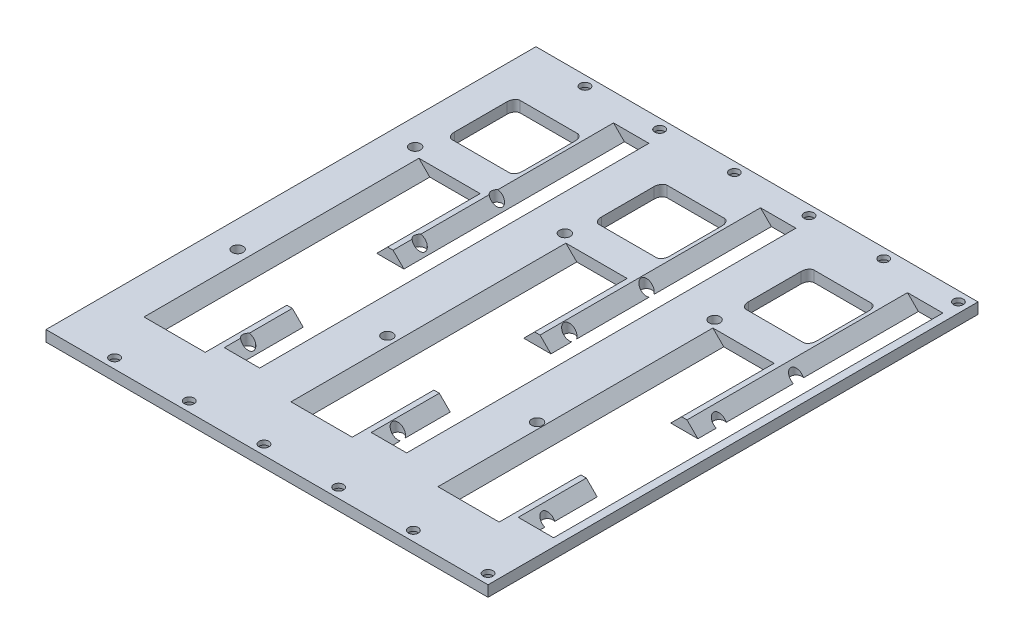
SolidWorks part; units mm, degrees
ref_plane "Płaszczyzna przednia" through (0, 0, 0) normal (0, 0, 1) x (1, 0, 0)
ref_plane "Płaszczyzna górna" through (0, 0, 0) normal (0, 1, 0) x (1, 0, 0)
ref_plane "Płaszczyzna prawa" through (0, 0, 0) normal (1, 0, 0) x (0, 0, -1)
sketch "Szkic1" plane through (0, 0, 0) normal (0, 1, 0) x (1, 0, 0)
  line L1 (-81.2, -90) -> (81.2, -90)
  line L2 (-81.2, -90) -> (-81.2, 90)
  line L3 (-81.2, 90) -> (81.2, 90)
  line L4 (81.2, -90) -> (81.2, 90)
  line L5 (0, 90) -> (0, -90) construction
  line L6 (-81.2, 0) -> (81.2, 0) construction
  point P0 (0, 0)
  dimension "D1" = 162.4
  dimension "D2" = 180
extrude "Dodanie-wyciągnięcie1" add sketch "Szkic1" along normal blind 4
sketch "Szkic2" plane through (0, 0, 0) normal (0, -1, 0) x (1, 0, 0)
  line L0 (-44, -47.8284) -> (-44, -67.1716) construction
  line L1 (-46, -70) -> (-67, -70) construction
  line L2 (-69, -67.1716) -> (-69, -47.8284) construction
  line L3 (-67, -45) -> (-46, -45) construction
  line L4 (-44, -47.8284) -> (-44, -67.1716)
  line L5 (-46, -70) -> (-67, -70)
  line L6 (-69, -67.1716) -> (-69, -47.8284)
  line L7 (-67, -45) -> (-46, -45)
  line L8 (81.2, -130) -> (-81.2, -130) construction
  line L9 (10, -47.8284) -> (10, -67.1716)
  line L10 (8, -70) -> (-13, -70)
  line L11 (-15, -67.1716) -> (-15, -47.8284)
  line L12 (-81.2, 90) -> (81.2, 90) construction
  line L13 (-81.2, -130) -> (-81.2, 90) construction
  line L15 (-13, -45) -> (8, -45)
  line L16 (-9.2, -33) -> (5.3, -33)
  line L17 (5.3, -33) -> (5.3, 1)
  line L18 (5.3, 1) -> (15.3, 1)
  line L19 (15.3, 1) -> (15.3, -80)
  line L20 (15.3, -80) -> (20.3, -80)
  line L21 (20.3, -80) -> (20.3, 63)
  line L22 (20.3, 63) -> (15.3, 63)
  line L23 (15.3, 63) -> (15.3, 38)
  line L24 (-63.2, -33) -> (-48.7, -33)
  line L25 (-48.7, -33) -> (-48.7, 1)
  line L26 (-48.7, 1) -> (-38.7, 1)
  line L27 (-38.7, 1) -> (-38.7, -80)
  line L28 (-38.7, -80) -> (-33.7, -80)
  line L29 (-33.7, -80) -> (-33.7, 63)
  line L30 (-33.7, 63) -> (-38.7, 63)
  line L31 (-38.7, 63) -> (-38.7, 38)
  line L32 (-38.7, 38) -> (-48.7, 38)
  line L33 (-48.7, 38) -> (-48.7, 68)
  line L34 (-48.7, 68) -> (-63.2, 68)
  line L35 (-63.2, 68) -> (-63.2, -33)
  line L36 (15.3, 38) -> (5.3, 38)
  line L37 (5.3, 38) -> (5.3, 68)
  line L38 (5.3, 68) -> (-9.2, 68)
  line L39 (-9.2, 68) -> (-9.2, -33)
  line L40 (64, -47.8284) -> (64, -67.1716)
  line L41 (62, -70) -> (41, -70)
  line L42 (39, -67.1716) -> (39, -47.8284)
  line L43 (41, -45) -> (62, -45)
  line L44 (44.8, -33) -> (59.3, -33)
  line L45 (59.3, -33) -> (59.3, 1)
  line L46 (59.3, 1) -> (69.3, 1)
  line L47 (69.3, 1) -> (69.3, -80)
  line L48 (69.3, -80) -> (74.3, -80)
  line L49 (74.3, -80) -> (74.3, 63)
  line L50 (74.3, 63) -> (69.3, 63)
  line L51 (69.3, 63) -> (69.3, 38)
  line L52 (69.3, 38) -> (59.3, 38)
  line L53 (59.3, 38) -> (59.3, 68)
  line L54 (59.3, 68) -> (44.8, 68)
  line L55 (44.8, 68) -> (44.8, -33)
  ellipse E0 centre (-46, -47.8284) end of major axis (-46, -45) minor radius 2 (-44, -47.8284) -> (-46, -45) ccw construction
  ellipse E1 centre (-46, -67.1716) end of major axis (-46, -64.3431) minor radius 2 (-46, -70) -> (-44, -67.1716) ccw construction
  ellipse E2 centre (-67, -67.1716) end of major axis (-67, -64.3431) minor radius 2 (-69, -67.1716) -> (-67, -70) ccw construction
  ellipse E3 centre (-67, -47.8284) end of major axis (-67, -45) minor radius 2 (-67, -45) -> (-69, -47.8284) ccw construction
  ellipse E4 centre (-46, -47.8284) end of major axis (-46, -45) minor radius 2 (-44, -47.8284) -> (-46, -45) ccw
  ellipse E5 centre (-46, -67.1716) end of major axis (-46, -64.3431) minor radius 2 (-46, -70) -> (-44, -67.1716) ccw
  ellipse E6 centre (-67, -67.1716) end of major axis (-67, -64.3431) minor radius 2 (-69, -67.1716) -> (-67, -70) ccw
  ellipse E7 centre (-67, -47.8284) end of major axis (-67, -45) minor radius 2 (-67, -45) -> (-69, -47.8284) ccw
  ellipse E8 centre (8, -47.8284) end of major axis (8, -45) minor radius 2 (10, -47.8284) -> (8, -45) ccw
  ellipse E9 centre (8, -67.1716) end of major axis (8, -64.3431) minor radius 2 (8, -70) -> (10, -67.1716) ccw
  ellipse E10 centre (-13, -67.1716) end of major axis (-13, -64.3431) minor radius 2 (-15, -67.1716) -> (-13, -70) ccw
  ellipse E11 centre (-13, -47.8284) end of major axis (-13, -45) minor radius 2 (-13, -45) -> (-15, -47.8284) ccw
  ellipse E12 centre (62, -47.8284) end of major axis (62, -45) minor radius 2 (64, -47.8284) -> (62, -45) ccw
  ellipse E13 centre (62, -67.1716) end of major axis (62, -64.3431) minor radius 2 (62, -70) -> (64, -67.1716) ccw
  ellipse E14 centre (41, -67.1716) end of major axis (41, -64.3431) minor radius 2 (39, -67.1716) -> (41, -70) ccw
  ellipse E15 centre (41, -47.8284) end of major axis (41, -45) minor radius 2 (41, -45) -> (39, -47.8284) ccw
  dimension "D1" = 22
  dimension "D2" = 14.5
  dimension "D3" = 18
  dimension "D4" = 10
  dimension "D5" = 5
  dimension "D6" = 5
  dimension "D7" = 25
  dimension "D8" = 37
  dimension "D9" = 97
  dimension "D10" = 47
  dimension "D12" = 54
  dimension "D11" = 3
extrude "Wytnij-wyciągnięcie1" cut sketch "Szkic2" against normal up to next
chamfer "Sfazowanie1" distance 4 angle 45 18 edges at (69.3, 4, -39.5) (74.3, 4, -8.5) (69.3, 4, 50.5) (59.3, 4, 53) (59.3, 4, -16) (44.8, 4, 17.5) (15.3, 4, -39.5) (15.3, 4, 50.5) (20.3, 4, -8.5) (5.3, 4, 53) (5.3, 4, -16) (-9.2, 4, 17.5) (-33.7, 4, -8.5) (-38.7, 4, -39.5) (-38.7, 4, 50.5) (-48.7, 4, 53) (-48.7, 4, -16) (-63.2, 4, 17.5)
sketch "Szkic3" plane through (0, 0, 0) normal (0, -1, 0) x (1, 0, 0)
  line L0 (81.2, 90) -> (81.2, -90) construction
  line L1 (81.2, -90) -> (-81.2, -90) construction
  line L2 (0, 0) -> (-81.2, 0) construction
  line L3 (-81.2, -90) -> (-81.2, 90) construction
  point P1 (77.6, -86.4)
  point P6 (50.16, -86.4)
  point P8 (22.72, -86.4)
  point P9 (-4.72, -86.4)
  point P10 (-32.16, -86.4)
  point P11 (-59.6, -86.4)
  point P15 (-59.6, 86.4)
  point P16 (-32.16, 86.4)
  point P17 (-4.72, 86.4)
  point P18 (22.72, 86.4)
  point P19 (50.16, 86.4)
  point P20 (77.6, 86.4)
  dimension "D1" = 3.6
  dimension "D2" = 3.6
  dimension "D4" = 27.44
  dimension "D3" = 6
hole_wizard "Pogłębienie walcowe pod M3 Śrubę z łbem stożkowym ściętym1" positions "Szkic3" profile "Szkic4" counterbore size "M3" standard "DIN"
sketch "Szkic4" plane through (77.6, 0, 86.4) normal (1, 0, 0) x (0, 0, -1)
  line L0 (0, 0) -> (0, 7.7815)
  line L1 (0, 7.7815) -> (1.8, 6.7)
  line L2 (1.8, 6.7) -> (1.8, 2.4)
  line L3 (1.8, 2.4) -> (3.5, 2.4)
  line L4 (3.5, 2.4) -> (3.5, 0)
  line L5 (3.5, 0) -> (0, 0)
  line L10 (0, 7.7815) -> (-1.8, 6.7) construction
  line L11 (0, -6.35) -> (0, 107.95) construction
  dimension "Średnica otworu" = 3.6
  dimension "Głębokość otworu" = 6.7
  dimension "Średnica pogłębienia walcowego" = 7
  dimension "Głębokość pogłębienia walcowego" = 2.4
  dimension "Kąt wiertła" = 118
sketch "Szkic5" plane through (0, 0, 0) normal (0, -1, 0) x (1, 0, 0)
  point P0 (-41.5, 55.44)
  point P1 (-71.5, 29.28)
  point P3 (-41.5, -35.92)
  point P5 (-71.5, -35.92)
  point P7 (-41.5, -7.56)
  point P11 (13.5, 55.44)
  point P12 (-16.5, 29.28)
  point P13 (13.5, -35.92)
  point P14 (-16.5, -35.92)
  point P15 (13.5, -7.56)
  point P16 (68.5, 55.44)
  point P17 (38.5, 29.28)
  point P18 (68.5, -35.92)
  point P19 (38.5, -35.92)
  point P20 (68.5, -7.56)
  dimension "D1" = 3
hole_wizard "Otwory ustalające Ø4.0mm1" positions "Szkic5" profile "Szkic6" hole size "Ø4.0" standard "DIN"
sketch "Szkic6" plane through (-41.5, 0, 55.44) normal (1, 0, 0) x (0, 0, -1)
  line L0 (0, 0) -> (0, 6.7)
  line L1 (0, 6.7) -> (2, 6.7)
  line L2 (2, 6.7) -> (2, 0)
  line L5 (2, 0) -> (0, 0)
  line L10 (0, 6.7) -> (-2, 6.7) construction
  line L11 (0, -6.35) -> (0, 107.95) construction
  dimension "Średnica otworu" = 4
  dimension "Głębokość otworu" = 6.7
  dimension "Kąt wiertła" = 180
